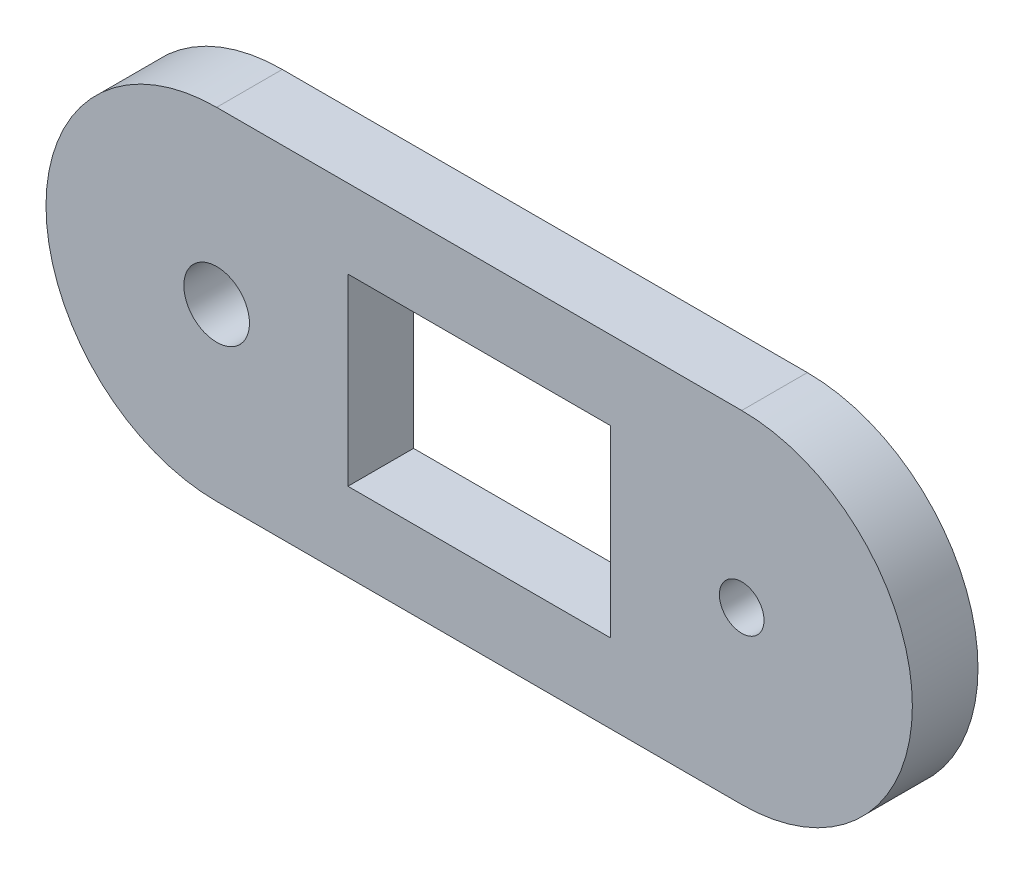
SolidWorks part; units mm, degrees
ref_plane "Front Plane" through (0, 0, 0) normal (0, 0, 1) x (1, 0, 0)
ref_plane "Top Plane" through (0, 0, 0) normal (0, 1, 0) x (1, 0, 0)
ref_plane "Right Plane" through (0, 0, 0) normal (1, 0, 0) x (0, 0, -1)
sketch "Sketch1" plane through (0, 0, 0) normal (0, 0, 1) x (1, 0, 0)
  line L1 (-25.4, 16.51) -> (25.4, 16.51)
  line L2 (-25.4, 16.51) -> (-25.4, -16.51)
  line L3 (-25.4, -16.51) -> (25.4, -16.51)
  line L4 (25.4, 16.51) -> (25.4, -16.51)
  line L5 (-25.4, 16.51) -> (25.4, -16.51) construction
  line L6 (-25.4, -16.51) -> (25.4, 16.51) construction
  line L7 (-12.7, 8.89) -> (12.7, 8.89)
  line L8 (-12.7, 8.89) -> (-12.7, -8.89)
  line L9 (-12.7, -8.89) -> (12.7, -8.89)
  line L10 (12.7, 8.89) -> (12.7, -8.89)
  line L11 (-12.7, 8.89) -> (12.7, -8.89) construction
  line L12 (-12.7, -8.89) -> (12.7, 8.89) construction
  arc A0 (25.4, -16.51) -> (25.4, 16.51) centre (25.4, 0) ccw
  arc A1 (-25.4, -16.51) -> (-25.4, 16.51) centre (-25.4, 0) cw
  circle A2 centre (25.4, 0) radius 2.159
  circle A3 centre (-25.4, 0) radius 3.175
  point P0 (0, 0)
  point P10 (0, 0)
  dimension "D3" = 6.35
  dimension "D4" = 4.318
  dimension "D1" = 33.02
  dimension "D2" = 50.8
  dimension "D5" = 12.7
  dimension "D6" = 7.62
extrude "Boss-Extrude1" add sketch "Sketch1" along normal blind 6.35 contours A3 L2 A1 | A3 L2 L3 L4 A2 L1 L7 L10 L9 L8 | A2 L4 A0 region at (0, 15.9041, 0) region at (-32.6244, 0, 0) region at (32.513, 0, 0)
sketch "Sketch2" plane through (0, 0, 6.35) normal (0, 0, 1) x (1, 0, 0)
  circle A0 centre (25.4, 0) radius 7.7596
  circle A1 centre (25.4, 0) radius 3.81
  dimension "D1" = 7.62
extrude "Boss-Extrude2" add sketch "Sketch2" against normal blind 1.27
